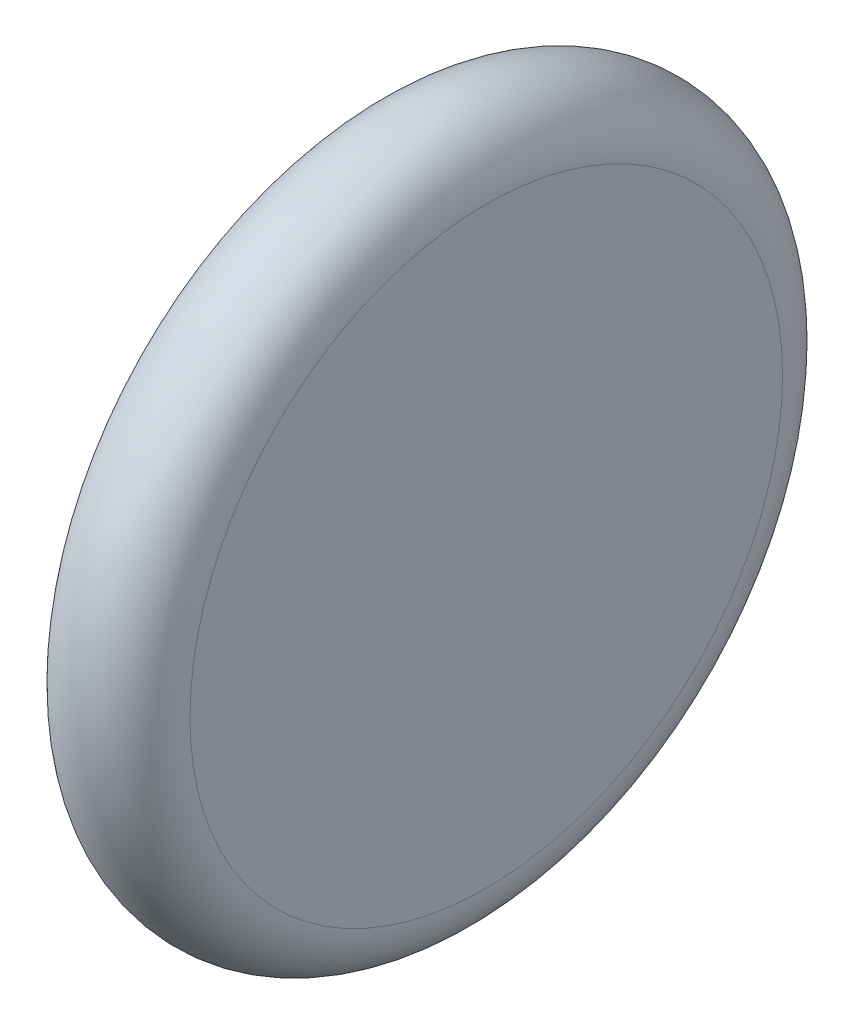
SolidWorks part; units mm, degrees
ref_plane "Front Plane" through (0, 0, 0) normal (0, 0, 1) x (1, 0, 0)
ref_plane "Top Plane" through (0, 0, 0) normal (0, 1, 0) x (1, 0, 0)
ref_plane "Right Plane" through (0, 0, 0) normal (1, 0, 0) x (0, 0, -1)
sketch "Sketch1" plane through (0, 0, 0) normal (0, 0, 1) x (1, 0, 0)
  line L0 (0, 0) -> (0, 5)
  line L1 (0, 5) -> (10, 5)
  line L2 (10, 5) -> (10, 25)
  line L3 (10, 25) -> (7, 25)
  line L4 (0, 0) -> (17, 0)
  line L13 (17, 0) -> (17, 30)
  line L14 (17, 30) -> (7, 30)
  line L15 (7, 30) -> (7, 25)
  dimension "D1" = 5
  dimension "D2" = 20
  dimension "D3" = 3
  dimension "D5" = 10
  dimension "D4" = 17
  dimension "D6" = 30
  dimension "D7" = 10
revolve "Revolve2" add sketch "Sketch1" angle 360 about L4
fillet "Fillet1" 2 edges at (17, 0, 30) (7, 0, 30) type full round first side face at (17, 0, 30) second side face at (7, 0, 25) middle face at (7, 0, 30)
